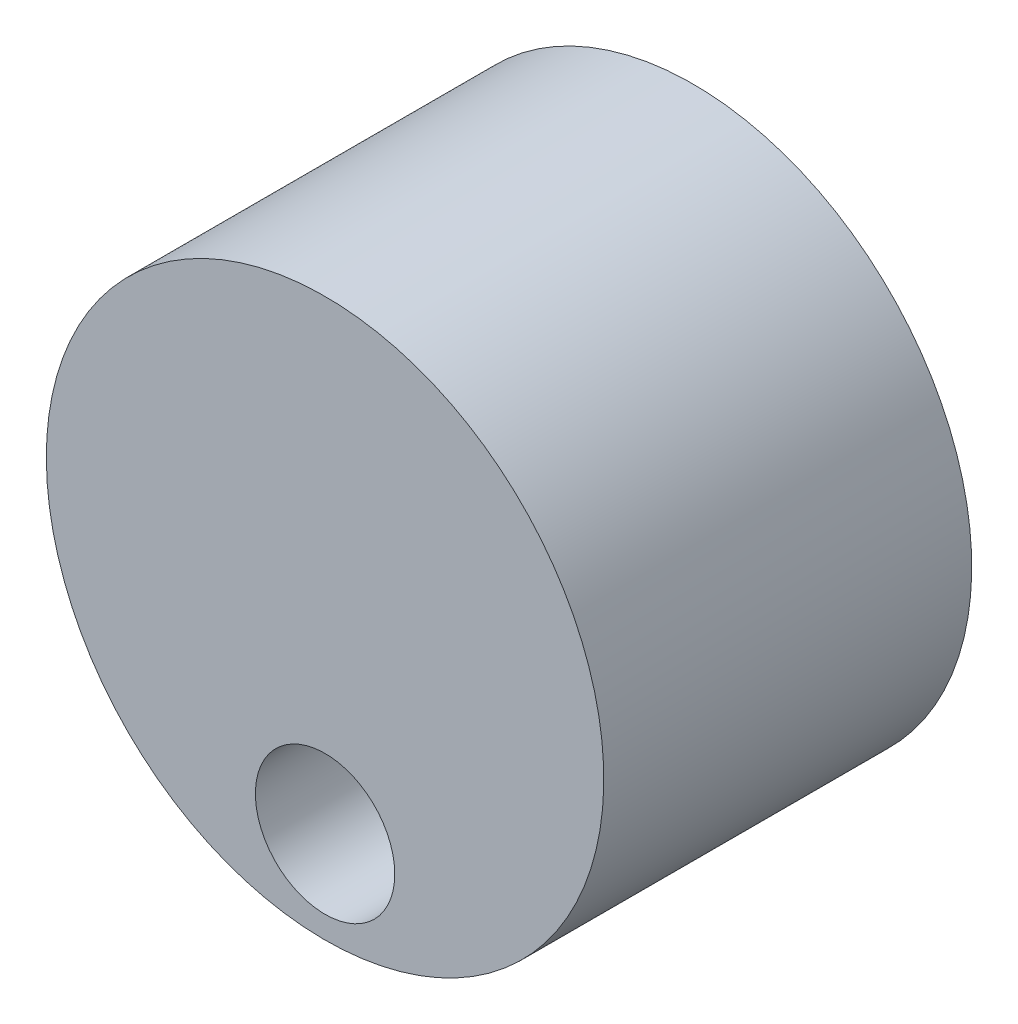
SolidWorks part; units mm, degrees
ref_plane "Plan de face" through (0, 0, 0) normal (0, 0, 1) x (1, 0, 0)
ref_plane "Plan de dessus" through (0, 0, 0) normal (0, 1, 0) x (1, 0, 0)
ref_plane "Plan de droite" through (0, 0, 0) normal (1, 0, 0) x (0, 0, -1)
sketch "Esquisse1" plane through (0, 0, 0) normal (0, 0, 1) x (1, 0, 0)
  line L0 (0, 0) -> (0, -8.509) construction
  ellipse E0 centre (0, 0) end of major axis (5.758, 11.3197) minor radius 12.7
  ellipse E1 centre (0, -8.509) end of major axis (-1.7944, -5.8897) minor radius 3.175
extrude "Boss.-Extru.1" add sketch "Esquisse1" along normal blind 16.764
